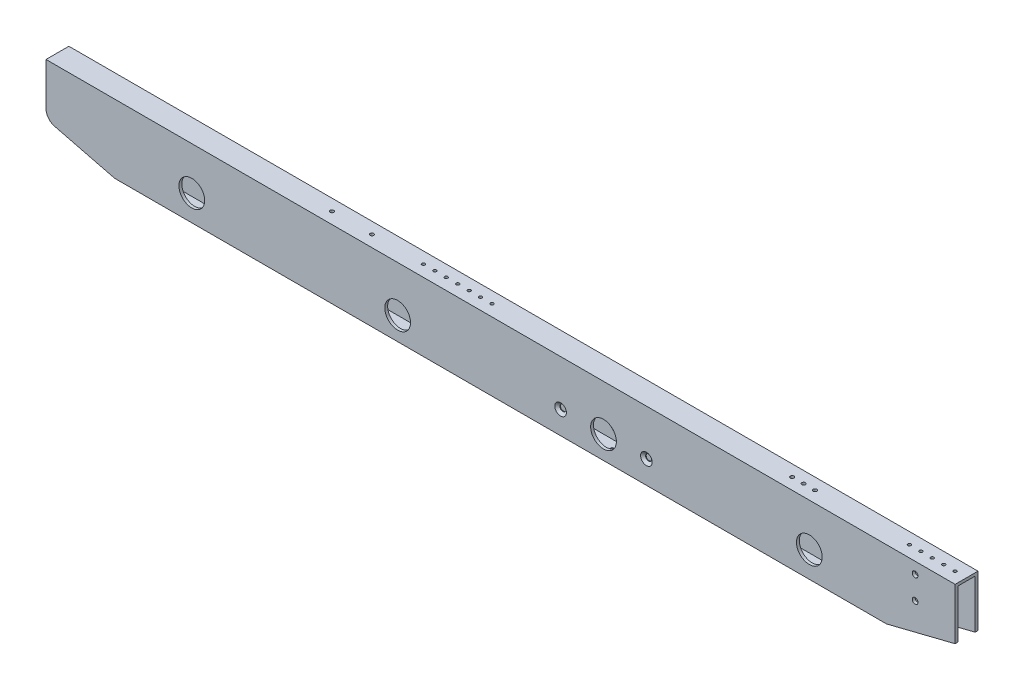
SolidWorks part; units mm, degrees
material "6061-T6 (SS)"
ref_plane "Front Plane" through (0, 0, 0) normal (0, 0, 1) x (1, 0, 0)
ref_plane "Top Plane" through (0, 0, 0) normal (0, 1, 0) x (1, 0, 0)
ref_plane "Right Plane" through (0, 0, 0) normal (1, 0, 0) x (0, 0, -1)
sketch "Sketch1" plane through (0, 0, 0) normal (0, 0, 1) x (1, 0, 0)
  line L0 (0, -12.7) -> (-342.9, -9.525) construction
  line L1 (-504.825, 38.1) -> (504.825, 38.1)
  line L2 (-504.825, 38.1) -> (-504.825, -38.1)
  line L3 (-504.825, -38.1) -> (504.825, -38.1)
  line L4 (504.825, 38.1) -> (504.825, -38.1)
  line L5 (-504.825, 38.1) -> (504.825, -38.1) construction
  line L6 (-504.825, -38.1) -> (504.825, 38.1) construction
  line L7 (-504.825, -38.1) -> (504.825, -38.1) construction
  line L8 (-504.825, -38.1) -> (-504.825, 12.7) construction
  line L9 (-339.7523, -73.025) -> (358.7477, -73.025) construction
  line L10 (-504.825, 12.7) -> (504.825, 12.7) construction
  line L11 (504.825, -38.1) -> (504.825, 12.7) construction
  line L12 (0, -12.7) -> (342.9, -9.525) construction
  line L13 (-114.3, -12.7) -> (114.3, -12.7) construction
  circle A0 centre (-114.3, -12.7) radius 14.2875
  circle A1 centre (114.3, -12.7) radius 14.2875
  circle A2 centre (-342.9, -9.525) radius 14.2875
  circle A3 centre (342.9, -9.525) radius 14.2875
  circle A4 centre (-342.9, -9.525) radius 63.5 construction
  circle A5 centre (-114.3, -12.7) radius 63.5 construction
  circle A6 centre (114.3, -12.7) radius 63.5 construction
  circle A7 centre (342.9, -9.525) radius 63.5 construction
  point P0 (0, 0)
  point P12 (0, -38.1)
  dimension "D5" = 228.6
  dimension "D4" = 50.8
  dimension "D8" = 228.6
  dimension "D9" = 28.575
  dimension "D6" = 28.575
  dimension "D10" = 127
  dimension "D1" = 76.2
  dimension "D2" = 1009.65
  dimension "D3" = 25.4
  dimension "D7" = 228.6
extrude "Boss-Extrude2" add sketch "Sketch1" along normal mid plane 25.4
sketch "Sketch3" plane through (504.825, 0, 0) normal (1, 0, 0) x (0, 0, -1)
  line L8 (9.525, -34.925) -> (9.525, 34.925)
  line L9 (9.525, 34.925) -> (-9.525, 34.925)
  line L10 (-9.525, 34.925) -> (-9.525, -34.925)
  line L11 (-9.525, -34.925) -> (9.525, -34.925)
  line L12 (9.525, -34.925) -> (9.525, 34.925)
  line L13 (9.525, 34.925) -> (-9.525, 34.925)
  line L14 (-9.525, 34.925) -> (-9.525, -34.925)
  line L15 (-9.525, -34.925) -> (9.525, -34.925)
  dimension "D1" = 3.175
extrude "Cut-Extrude2" cut sketch "Sketch3" against normal through all
sketch "Sketch4" plane through (0, 0, 12.7) normal (0, 0, 1) x (1, 0, 0)
  line L0 (-504.825, -38.1) -> (-504.825, -19.05)
  line L1 (-504.825, 38.1) -> (-504.825, -38.1) construction
  line L2 (-504.825, -19.05) -> (-428.625, -38.1)
  line L3 (-504.825, -38.1) -> (504.825, -38.1) construction
  line L4 (-428.625, -38.1) -> (-504.825, -38.1)
  line L5 (0, -38.1) -> (0, 38.1) construction
  line L6 (504.825, 38.1) -> (-504.825, 38.1) construction
  line L7 (428.625, -38.1) -> (504.825, -38.1)
  line L8 (504.825, -38.1) -> (504.825, -19.05)
  line L9 (504.825, -19.05) -> (428.625, -38.1)
  line L11 (504.825, -19.05) -> (504.825, 38.1) construction
  point P15 (0, 0)
  dimension "D1" = 19.05
  dimension "D2" = 57.15
  dimension "D3" = 76.2
  dimension "D4" = 504.825
  dimension "D5" = 14.036
extrude "Cut-Extrude3" cut sketch "Sketch4" against normal through all
fillet "Fillet1" radius 12.7 2 edges at (-504.825, -19.05, -11.1125) (-504.825, -19.05, 11.1125)
sketch "Sketch9" plane through (0, 38.1, 0) normal (0, 1, 0) x (1, 0, 0)
  line L0 (504.825, -12.7) -> (504.825, 12.7) construction
  circle A0 centre (492.125, 0) radius 1.7272
  circle A1 centre (479.425, 0) radius 1.7272
  circle A2 centre (466.725, 0) radius 1.7272
  circle A3 centre (454.025, 0) radius 1.7272
  circle A4 centre (441.325, 0) radius 1.7272
  point P2 (504.825, 0)
  dimension "D1" = 3.4544
  dimension "D2" = 12.7
  dimension "D3" = 4
  dimension "D4" = 2
extrude "Cut-Extrude4" cut sketch "Sketch9" against normal blind 2.54
sketch "Sketch12" plane through (0, 38.1, 0) normal (0, 1, 0) x (1, 0, 0)
  line L0 (-504.825, -12.7) -> (-504.825, 12.7) construction
  circle A0 centre (-98.425, 0) radius 1.7272
  circle A1 centre (-85.725, 0) radius 1.7272
  circle A2 centre (-73.025, 0) radius 1.7272
  circle A3 centre (-60.325, 0) radius 1.7272
  circle A4 centre (-47.625, 0) radius 1.7272
  circle A5 centre (-34.925, 0) radius 1.7272
  circle A6 centre (-22.225, 0) radius 1.7272
  point P5 (-28.575, 0)
  point P15 (-504.825, 0)
  dimension "D1" = 3.4544
  dimension "D2" = 406.4
  dimension "D4" = 476.25
  dimension "D3" = 7
extrude "Cut-Extrude7" cut sketch "Sketch12" against normal blind 5.08
hole_wizard "CSK for 1/4 Flat Head Machine Screw (100)2" positions "Sketch16" profile "Sketch15" countersink size "1/4" standard "ANSI Inch" end condition through all
sketch "Sketch16" plane through (0, 0, 12.7) normal (0, 0, 1) x (1, 0, 0)
  circle A0 centre (114.3, -12.7) radius 14.2875 construction
  point P4 (66.675, -12.7)
  point P6 (161.925, -12.7)
  dimension "D1" = 47.625
  dimension "D2" = 47.625
sketch "Sketch15" plane through (66.675, -12.7, 12.7) normal (1, 0, 0) x (0, -1, 0)
  line L0 (0, 0) -> (0, 25.4)
  line L1 (0, 25.4) -> (3.3782, 25.4)
  line L2 (3.3782, 25.4) -> (3.3782, 2.5682)
  line L3 (3.3782, 2.5682) -> (6.4389, 0)
  line L5 (6.4389, 0) -> (0, 0)
  line L6 (-3.3782, 2.5682) -> (-6.4389, 0) construction
  line L11 (0, -6.35) -> (0, 107.95) construction
  dimension "Thru Hole Dia." = 6.7564
  dimension "Thru Hole Depth" = 25.4
  dimension "Near C'Sink Dia." = 12.8778
  dimension "Near C'Sink Angle" = 100
sketch "Sketch17" plane through (0, -38.1, 0) normal (0, -1, 0) x (-1, 0, 0)
  line L0 (-428.625, 12.7) -> (-428.625, -12.7) construction
  circle A0 centre (-415.925, 0) radius 1.7272
  circle A1 centre (-396.875, 0) radius 1.7272
  circle A2 centre (-377.825, 0) radius 1.7272
  circle A3 centre (-358.775, 0) radius 1.7272
  circle A4 centre (-339.725, 0) radius 1.7272
  circle A5 centre (-320.675, 0) radius 1.7272
  circle A6 centre (-301.625, 0) radius 1.7272
  circle A7 centre (-282.575, 0) radius 1.7272
  circle A8 centre (-263.525, 0) radius 1.7272
  circle A9 centre (-244.475, 0) radius 1.7272
  circle A10 centre (-225.425, 0) radius 1.7272
  circle A11 centre (-206.375, 0) radius 1.7272
  circle A12 centre (-187.325, 0) radius 1.7272
  circle A13 centre (-168.275, 0) radius 1.7272
  circle A14 centre (-149.225, 0) radius 1.7272
  circle A15 centre (-130.175, 0) radius 1.7272
  circle A16 centre (-111.125, 0) radius 1.7272
  circle A17 centre (-92.075, 0) radius 1.7272
  circle A18 centre (-73.025, 0) radius 1.7272
  circle A19 centre (-53.975, 0) radius 1.7272
  circle A20 centre (-34.925, 0) radius 1.7272
  circle A21 centre (-15.875, 0) radius 1.7272
  circle A22 centre (3.175, 0) radius 1.7272
  circle A23 centre (22.225, 0) radius 1.7272
  circle A24 centre (41.275, 0) radius 1.7272
  circle A25 centre (60.325, 0) radius 1.7272
  point P2 (-428.625, 0)
  dimension "D1" = 3.4544
  dimension "D2" = 12.7
  dimension "D3" = 26
extrude "Cut-Extrude8" cut sketch "Sketch17" against normal blind 6.35
sketch "Sketch18" plane through (0, 0, -12.7) normal (0, 0, -1) x (-1, 0, 0)
  circle A0 centre (-114.3, -12.7) radius 17.4625
  dimension "D1" = 34.925
extrude "Cut-Extrude9" cut sketch "Sketch18" against normal blind 3.81
hole_wizard "1/4 (0.25) Diameter Hole1" positions "Sketch20" profile "Sketch19" hole size "1/4" standard "ANSI Inch" end condition through all
sketch "Sketch20" plane through (0, 0, 12.7) normal (0, 0, 1) x (1, 0, 0)
  line L0 (504.825, -19.05) -> (504.825, 38.1) construction
  line L1 (504.825, 38.1) -> (-504.825, 38.1) construction
  point P0 (460.375, 25.4)
  point P2 (460.375, 0)
  dimension "D1" = 25.4
  dimension "D2" = 44.45
  dimension "D3" = 12.7
sketch "Sketch19" plane through (460.375, 25.4, 12.7) normal (1, 0, 0) x (0, -1, 0)
  line L0 (0, 0) -> (0, 25.4)
  line L1 (0, 25.4) -> (3.175, 25.4)
  line L2 (3.175, 25.4) -> (3.175, 0)
  line L5 (3.175, 0) -> (0, 0)
  line L11 (0, -6.35) -> (0, 107.95) construction
  dimension "Thru Hole Dia." = 6.35
  dimension "Thru Hole Depth" = 25.4
hole_wizard "#10-32 Tapped Hole1" positions "Sketch22" profile "Sketch21" tap size "#10-32" standard "ANSI Inch"
sketch "Sketch22" plane through (0, 38.1, 0) normal (0, 1, 0) x (1, 0, 0)
  circle A0 centre (-60.325, 0) radius 1.7272 construction
  point P0 (-155.575, 0)
  point P2 (-200.025, 0)
  dimension "D1" = 95.25
  dimension "D2" = 44.45
cosmetic thread "Hole Thread1" parameters "D1"=3.175, "D2"=4.826
cosmetic thread "Hole Thread2" parameters "D1"=3.175, "D2"=4.826
sketch "Sketch21" plane through (-155.575, 38.1, 0) normal (1, 0, 0) x (0, 0, 1)
  line L0 (0, 0) -> (0, 14.9293)
  line L1 (0, 14.9293) -> (2.0193, 13.716)
  line L2 (2.0193, 13.716) -> (2.0193, 0)
  line L5 (2.0193, 0) -> (0, 0)
  line L10 (0, 14.9293) -> (-2.0193, 13.716) construction
  line L11 (0, -6.35) -> (0, 107.95) construction
  dimension "Tap Drill Dia." = 4.0386
  dimension "Tap Drill Depth" = 13.716
  dimension "Drill Angle" = 118
hole_wizard "#10-32 Tapped Hole2" positions "Sketch24" profile "Sketch23" tap size "#10-32" standard "ANSI Inch" end condition through all
sketch "Sketch24" plane through (0, 38.1, 0) normal (0, 1, 0) x (1, 0, 0)
  line L0 (504.825, -12.7) -> (504.825, 12.7) construction
  point P0 (336.55, 0)
  point P2 (323.85, 0)
  point P4 (311.15, 0)
  dimension "D1" = 168.275
  dimension "D2" = 12.7
  dimension "D3" = 12.7
sketch "Sketch23" plane through (336.55, 38.1, 0) normal (1, 0, 0) x (0, 0, 1)
  line L0 (0, 0) -> (0, 76.2)
  line L1 (0, 76.2) -> (2.0193, 76.2)
  line L2 (2.0193, 76.2) -> (2.0193, 0)
  line L5 (2.0193, 0) -> (0, 0)
  line L11 (0, -6.35) -> (0, 107.95) construction
  dimension "Thread Major Dia." = 4.0386
  dimension "Thru Tap Drill Depth" = 76.2
